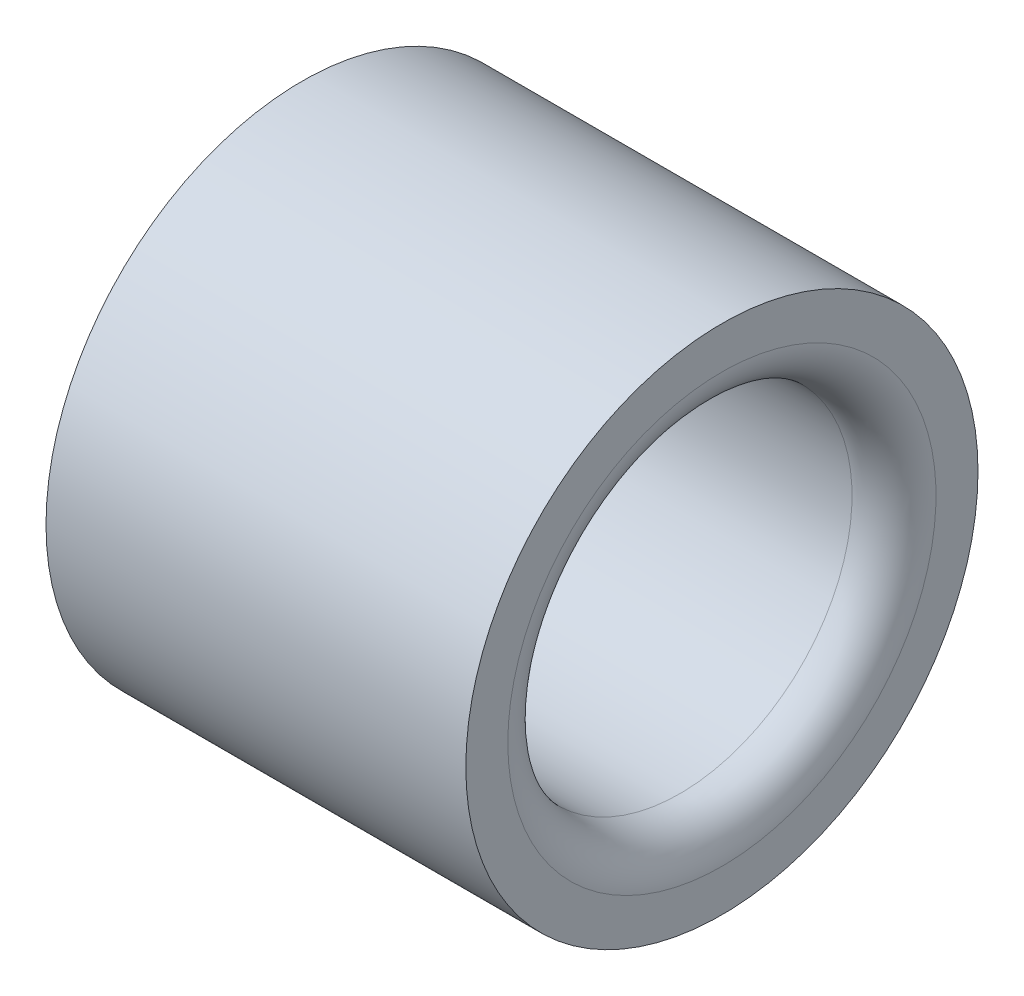
SolidWorks part; units mm, degrees
ref_plane "Front Plane" through (0, 0, 0) normal (0, 0, 1) x (1, 0, 0)
ref_plane "Top Plane" through (0, 0, 0) normal (0, 1, 0) x (1, 0, 0)
ref_plane "Right Plane" through (0, 0, 0) normal (1, 0, 0) x (0, 0, -1)
sketch "Sketch1" plane through (0, 0, 0) normal (0, 0, 1) x (1, 0, 0)
  line L0 (0, 2.6) -> (1.4236, 2.6)
  line L1 (1.4236, 2.6) -> (1.4236, 4.1)
  line L2 (1.4236, 4.1) -> (10, 4.1)
  line L3 (10, 4.1) -> (10, 6.1)
  line L4 (10, 6.1) -> (0, 6.1)
  line L5 (0, 6.1) -> (0, 2.6)
  line L6 (0, 0) -> (6.7708, 0) construction
  dimension "D1" = 5.2
  dimension "D2" = 8.2
  dimension "D3" = 10
  dimension "D4" = 2
revolve "Revolve1" add sketch "Sketch1" angle 360 about L6
fillet "Fillet1" radius 1 1 edges at (10, 0, 4.1)
